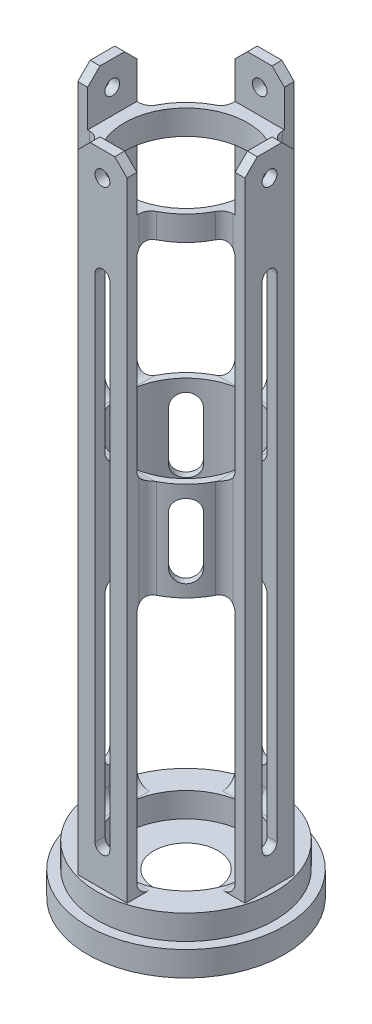
SolidWorks part; units mm, degrees
material "尼龙 101"
ref_plane "前视基准面" through (0, 0, 0) normal (0, 0, 1) x (1, 0, 0)
ref_plane "上视基准面" through (0, 0, 0) normal (0, 1, 0) x (1, 0, 0)
ref_plane "右视基准面" through (0, 0, 0) normal (1, 0, 0) x (0, 0, -1)
other "Configuration Table"
sketch "草图1" plane through (0, 0, 0) normal (0, 1, 0) x (1, 0, 0)
  circle A0 centre (0, 0) radius 20
  circle A1 centre (0, 0) radius 6.5
  dimension "D1" = 40
  dimension "D2" = 13
extrude "凸台-拉伸2" add sketch "草图1" along normal blind 5
sketch "草图3" plane through (0, 0, 0) normal (0, 1, 0) x (1, 0, 0)
  circle A0 centre (0, 0) radius 18
  circle A1 centre (0, 0) radius 12.5
  dimension "D1" = 36
  dimension "D2" = 25
extrude "凸台-拉伸3" add sketch "草图3" along normal blind 5 from offset 5
sketch "草图4" plane through (0, 0, 0) normal (0, 0, 1) x (1, 0, 0)
  line L0 (0, -1000) -> (0, 49000) construction
  line L1 (20, 0) -> (6.5, 5)
  line L2 (-20, 0) -> (20, 0) construction
  line L3 (20, 5) -> (-20, 5) construction
  line L4 (6.5, 5) -> (-6.5, 5) construction
  line L5 (6.5, 5) -> (6.5, 0)
  line L6 (-6.5, 0) -> (6.5, 0) construction
  line L7 (6.5, 0) -> (20, 0)
  dimension "D1" = 13.5
revolve "切除-旋转1" cut sketch "草图4" angle 360 about L0
sketch "草图5" plane through (0, 0, 0) normal (0, 1, 0) x (1, 0, 0)
  line L0 (-1000, 0) -> (49000, 0) construction
  line L1 (0, -1000) -> (0, 49000) construction
  line L2 (-707.1068, -707.1068) -> (34648.2323, 34648.2323) construction
  line L3 (707.1068, -707.1068) -> (-34648.2323, 34648.2323) construction
  line L4 (-5, 14.9666) -> (5, 14.9666)
  line L5 (-5, 14.9666) -> (5, 14.9666)
  line L6 (5, 14.9666) -> (5, 16.9666)
  line L7 (5, 16.9666) -> (-5, 16.9666)
  line L8 (-5, 16.9666) -> (-5, 14.9666)
  line L9 (5, -14.9666) -> (5, -16.9666)
  line L10 (-5, -14.9666) -> (5, -14.9666)
  line L11 (-5, -16.9666) -> (-5, -14.9666)
  line L12 (5, -16.9666) -> (-5, -16.9666)
  line L13 (-14.9666, 5) -> (-16.9666, 5)
  line L14 (-16.9666, -5) -> (-14.9666, -5)
  line L15 (-16.9666, 5) -> (-16.9666, -5)
  line L16 (-14.9666, -5) -> (-14.9666, 5)
  line L17 (14.9666, 5) -> (16.9666, 5)
  line L18 (16.9666, 5) -> (16.9666, -5)
  line L19 (16.9666, -5) -> (14.9666, -5)
  line L20 (14.9666, -5) -> (14.9666, 5)
  circle A0 centre (0, 0) radius 20 construction
  circle A1 centre (0, 0) radius 20
  circle A2 centre (0, 0) radius 18 construction
  circle A3 centre (0, 0) radius 18
  point P17 (0, 14.9666)
  point P20 (0, 14.9666)
  dimension "D2" = 10
  dimension "D3" = 2
extrude "凸台-拉伸4" add sketch "草图5" along normal blind 130 from offset 10 contours L7 L8 L4 L6 | L14 L16 L13 L15 | L20 L19 L18 L17 | L12 L11 L10 L9 region at (0, 0, -15.9666) region at (-15.9666, 0, 0) region at (15.9666, 0, 0)
sketch "草图7" plane through (0, 0, 0) normal (0, 1, 0) x (1, 0, 0)
  line L0 (-5, 14.9666) -> (5, 14.9666) construction
  line L1 (-5, -14.9666) -> (5, -14.9666) construction
  line L2 (-5, 14.9666) -> (5, 14.9666)
  line L3 (-14.9666, -5) -> (-14.9666, 5) construction
  line L4 (-14.9666, -5) -> (-14.9666, 5)
  line L5 (14.9666, -5) -> (14.9666, 5) construction
  line L6 (14.9666, -5) -> (14.9666, 5)
  line L7 (-5, -14.9666) -> (5, -14.9666)
  line L8 (5, 14.9666) -> (5, 12.9666)
  line L9 (-5, 14.9666) -> (-5, 12.9666)
  line L10 (14.9666, 5) -> (12.9666, 5)
  line L11 (14.9666, -5) -> (12.9666, -5)
  line L12 (5, -14.9666) -> (5, -12.9666)
  line L13 (-5, -14.9666) -> (-5, -12.9666)
  line L14 (-14.9666, 5) -> (-12.9666, 5)
  line L15 (-14.9666, -5) -> (-12.9666, -5)
  circle A1 centre (0, 0) radius 12.5 construction
  circle A2 centre (0, 0) radius 12.5
  arc A6 (-5, 12.9666) -> (-12.9666, 5) centre (0, 0) ccw
  arc A7 (-12.9666, -5) -> (-5, -12.9666) centre (0, 0) ccw
  arc A8 (12.9666, 5) -> (5, 12.9666) centre (0, 0) ccw
  arc A9 (5, -12.9666) -> (12.9666, -5) centre (0, 0) ccw
  dimension "D1" = 27.7945
  dimension "D2" = 2
extrude "凸台-拉伸5" add sketch "草图7" along normal blind 10 and the other way blind 10 from offset 72.5
sketch "草图8" plane through (0, 0, 0) normal (0, 1, 0) x (1, 0, 0)
  line L4 (-14.9666, 5) -> (-14.9666, -5)
  line L5 (-5, -14.9666) -> (5, -14.9666)
  line L6 (14.9666, -5) -> (14.9666, 5)
  line L7 (5, 14.9666) -> (-5, 14.9666)
  line L8 (-14.9666, 5) -> (-14.9666, -5)
  line L9 (-5, -14.9666) -> (5, -14.9666)
  line L10 (14.9666, -5) -> (14.9666, 5)
  line L11 (5, 14.9666) -> (-5, 14.9666)
  line L20 (-5, 14.9666) -> (-5, 12.9666)
  line L21 (-5, 14.9666) -> (-5, 12.9666)
  line L22 (-12.9666, 5) -> (-14.9666, 5)
  line L23 (-12.9666, 5) -> (-14.9666, 5)
  line L24 (-14.9666, -5) -> (-12.9666, -5)
  line L25 (-14.9666, -5) -> (-12.9666, -5)
  line L26 (-5, -12.9666) -> (-5, -14.9666)
  line L27 (-5, -12.9666) -> (-5, -14.9666)
  line L28 (5, -14.9666) -> (5, -12.9666)
  line L29 (5, -14.9666) -> (5, -12.9666)
  line L30 (12.9666, -5) -> (14.9666, -5)
  line L31 (12.9666, -5) -> (14.9666, -5)
  line L32 (14.9666, 5) -> (12.9666, 5)
  line L33 (14.9666, 5) -> (12.9666, 5)
  line L34 (5, 12.9666) -> (5, 14.9666)
  line L35 (5, 12.9666) -> (5, 14.9666)
  circle A0 centre (0, 0) radius 12.5 construction
  circle A1 centre (0, 0) radius 12.5
  arc A4 (-5, 12.9666) -> (-12.9666, 5) centre (0, 0) ccw
  arc A5 (-5, 12.9666) -> (-12.9666, 5) centre (0, 0) ccw
  arc A6 (-12.9666, -5) -> (-5, -12.9666) centre (0, 0) ccw
  arc A7 (-12.9666, -5) -> (-5, -12.9666) centre (0, 0) ccw
  arc A14 (5, -12.9666) -> (12.9666, -5) centre (0, 0) ccw
  arc A15 (5, -12.9666) -> (12.9666, -5) centre (0, 0) ccw
  arc A16 (12.9666, 5) -> (5, 12.9666) centre (0, 0) ccw
  arc A17 (12.9666, 5) -> (5, 12.9666) centre (0, 0) ccw
  dimension "D1" = 0
extrude "凸台-拉伸6" add sketch "草图8" along normal blind 5 from offset 125
ref_plane "支撑槽口1" through (0, 0, 0) normal (-0.7071, 0, 0.7071) x (0, -1, 0)
sketch "草图9" plane through (0, 0, 0) normal (-0.7071, 0, 0.7071) x (0, -1, 0)
  line L0 (-82.5, 5.6333) -> (-62.5, -5.6333) construction
  line L1 (-82.5, 5.6333) -> (-62.5, 5.6333) construction
  line L2 (-82.5, 5.6333) -> (-82.5, -5.6333) construction
  line L3 (-82.5, -5.6333) -> (-62.5, -5.6333) construction
  line L4 (-62.5, 5.6333) -> (-62.5, -5.6333) construction
  line L5 (-62.5, -5.6333) -> (-62.5, 5.6333) construction
  line L6 (-62.5, 5.6333) -> (-82.5, -5.6333) construction
  line L7 (-77.5, 0) -> (-67.5, 0) construction
  line L8 (-77.5, 2.5) -> (-67.5, 2.5)
  line L9 (-77.5, -2.5) -> (-67.5, -2.5)
  arc A0 (-77.5, 2.5) -> (-77.5, -2.5) centre (-77.5, 0) ccw
  arc A1 (-67.5, -2.5) -> (-67.5, 2.5) centre (-67.5, 0) ccw
  point P8 (-72.5, 0)
extrude "切除-拉伸1" cut sketch "草图9" against normal through all and the other way through all
ref_plane "支撑槽口2" through (4.9833, 0, 4.9833) normal (-0.7071, 0, -0.7071) x (0, -1, 0)
sketch "草图10" plane through (4.9833, 0, 4.9833) normal (-0.7071, 0, -0.7071) x (0, -1, 0)
  line L0 (-82.5, 5.6333) -> (-62.5, -5.6333) construction
  line L1 (-82.5, 5.6333) -> (-62.5, 5.6333) construction
  line L2 (-82.5, 5.6333) -> (-82.5, -5.6333) construction
  line L3 (-82.5, -5.6333) -> (-62.5, -5.6333) construction
  line L4 (-62.5, 5.6333) -> (-62.5, -5.6333) construction
  line L5 (-62.5, 5.6333) -> (-82.5, -5.6333) construction
  line L6 (-77.5, 0) -> (-67.5, 0) construction
  line L7 (-77.5, 2.5) -> (-67.5, 2.5)
  line L8 (-77.5, -2.5) -> (-67.5, -2.5)
  arc A0 (-77.5, 2.5) -> (-77.5, -2.5) centre (-77.5, 0) ccw
  arc A1 (-67.5, -2.5) -> (-67.5, 2.5) centre (-67.5, 0) ccw
  point P8 (-72.5, 0)
extrude "切除-拉伸2" cut sketch "草图10" against normal through all and the other way through all
sketch "草图11" plane through (0, 0, 0) normal (0, 0, 1) x (1, 0, 0)
  line L1 (-5, 125) -> (5, 10) construction
  line L2 (-5, 125) -> (5, 125) construction
  line L3 (-5, 125) -> (-5, 10) construction
  line L4 (-5, 10) -> (5, 10) construction
  line L5 (5, 125) -> (5, 10) construction
  line L6 (5, 125) -> (-5, 10) construction
  line L7 (0, 17.5) -> (0, 117.5) construction
  line L8 (-1.5, 17.5) -> (-1.5, 117.5)
  line L9 (1.5, 17.5) -> (1.5, 117.5)
  arc A0 (-1.5, 17.5) -> (1.5, 17.5) centre (0, 17.5) ccw
  arc A1 (1.5, 117.5) -> (-1.5, 117.5) centre (0, 117.5) ccw
  point P8 (0, 67.5)
extrude "切除-拉伸3" cut sketch "草图11" against normal through all and the other way through all
sketch "草图12" plane through (0, 0, 0) normal (1, 0, 0) x (0, 0, -1)
  line L0 (5, 10) -> (-5, 10) construction
  line L1 (-5, 125) -> (5, 125) construction
  line L2 (-5, 125) -> (-5, 10) construction
  line L3 (-5, 10) -> (5, 10) construction
  line L4 (5, 125) -> (5, 10) construction
  line L5 (5, 125) -> (-5, 10) construction
  line L6 (5, 10) -> (-5, 125) construction
  line L7 (0, 17.5) -> (0, 117.5) construction
  line L8 (-1.5, 17.5) -> (-1.5, 117.5)
  line L9 (1.5, 17.5) -> (1.5, 117.5)
  arc A0 (-1.5, 17.5) -> (1.5, 17.5) centre (0, 17.5) ccw
  arc A1 (1.5, 117.5) -> (-1.5, 117.5) centre (0, 117.5) ccw
  point P9 (0, 67.5)
extrude "切除-拉伸4" cut sketch "草图12" against normal through all and the other way through all
fillet "圆角1" radius 2.5 4 edges at (14.9666, 10, 0) (0, 10, 14.9666) (-14.9666, 10, 0) (0, 10, -14.9666)
fillet "圆角2" radius 2.5 4 edges at (-14.9666, 125, 0) (0, 125, -14.9666) (14.9666, 125, 0) (0, 125, 14.9666)
fillet "圆角3" radius 2.5 16 edges at (-14.9666, 62.5, -3.25) (-14.9666, 62.5, 3.25) (-3.25, 62.5, -14.9666) (3.25, 62.5, -14.9666) (14.9666, 62.5, 3.25) (14.9666, 62.5, -3.25) (-3.25, 82.5, -14.9666) (3.25, 82.5, -14.9666) (14.9666, 82.5, -3.25) (14.9666, 82.5, 3.25) (3.25, 82.5, 14.9666) (-3.25, 82.5, 14.9666) (-14.9666, 82.5, 3.25) (-14.9666, 82.5, -3.25) (3.25, 62.5, 14.9666) (-3.25, 62.5, 14.9666)
fillet "圆角4" radius 2.5 16 edges at (-12.9666, 72.5, 5) (-5, 72.5, 12.9666) (-12.9666, 127.4747, 5) (-5, 127.4747, 12.9666) (5, 127.4747, 12.9666) (12.9666, 127.4747, 5) (12.9666, 72.5, 5) (5, 127.4747, -12.9666) (12.9666, 127.4747, -5) (5, 72.5, -12.9666) (12.9666, 72.5, -5) (-12.9666, 72.5, -5) (5, 72.5, 12.9666) (-12.9666, 127.4747, -5) (-5, 127.4747, -12.9666) (-5, 72.5, -12.9666)
sketch "草图13" plane through (0, 0, 0) normal (0, 0, 1) x (1, 0, 0)
  line L0 (5, 140) -> (-5, 130) construction
  line L1 (-5, 140) -> (5, 140) construction
  line L2 (-5, 140) -> (-5, 130) construction
  line L3 (-5, 130) -> (5, 130) construction
  line L4 (5, 140) -> (5, 130) construction
  line L5 (-5, 140) -> (5, 130) construction
  line L6 (5, 140) -> (2.5, 140)
  line L7 (5, 140) -> (5, 137.5)
  line L8 (5, 137.5) -> (2.5, 140)
  line L9 (-5, 140) -> (-2.5, 140)
  line L10 (-2.5, 140) -> (-5, 137.5)
  line L11 (-5, 140) -> (-5, 137.5)
  circle A0 centre (0, 135) radius 1.5
  dimension "D1" = 3
  dimension "D2" = 2.5
  dimension "D3" = 2.5
  dimension "D4" = 2.5
  dimension "D5" = 2.5
extrude "切除-拉伸5" cut sketch "草图13" against normal through all and the other way through all
sketch "草图14" plane through (0, 0, 0) normal (1, 0, 0) x (0, 0, -1)
  line L0 (5, 140) -> (-5, 130) construction
  line L1 (-5, 140) -> (5, 140) construction
  line L2 (-5, 140) -> (-5, 130) construction
  line L3 (-5, 130) -> (5, 130) construction
  line L4 (5, 140) -> (5, 130) construction
  line L5 (5, 130) -> (-5, 140) construction
  line L6 (5, 140) -> (5, 137.5)
  line L7 (5, 140) -> (2.5, 140)
  line L8 (2.5, 140) -> (5, 137.5)
  line L9 (-5, 140) -> (-2.5, 140)
  line L10 (-5, 140) -> (-5, 137.5)
  line L11 (-5, 137.5) -> (-2.5, 140)
  circle A0 centre (0, 135) radius 1.5
  dimension "D1" = 3
  dimension "D2" = 2.5
  dimension "D3" = 2.5
  dimension "D4" = 2.5
  dimension "D5" = 2.5
extrude "切除-拉伸6" cut sketch "草图14" against normal through all and the other way through all
